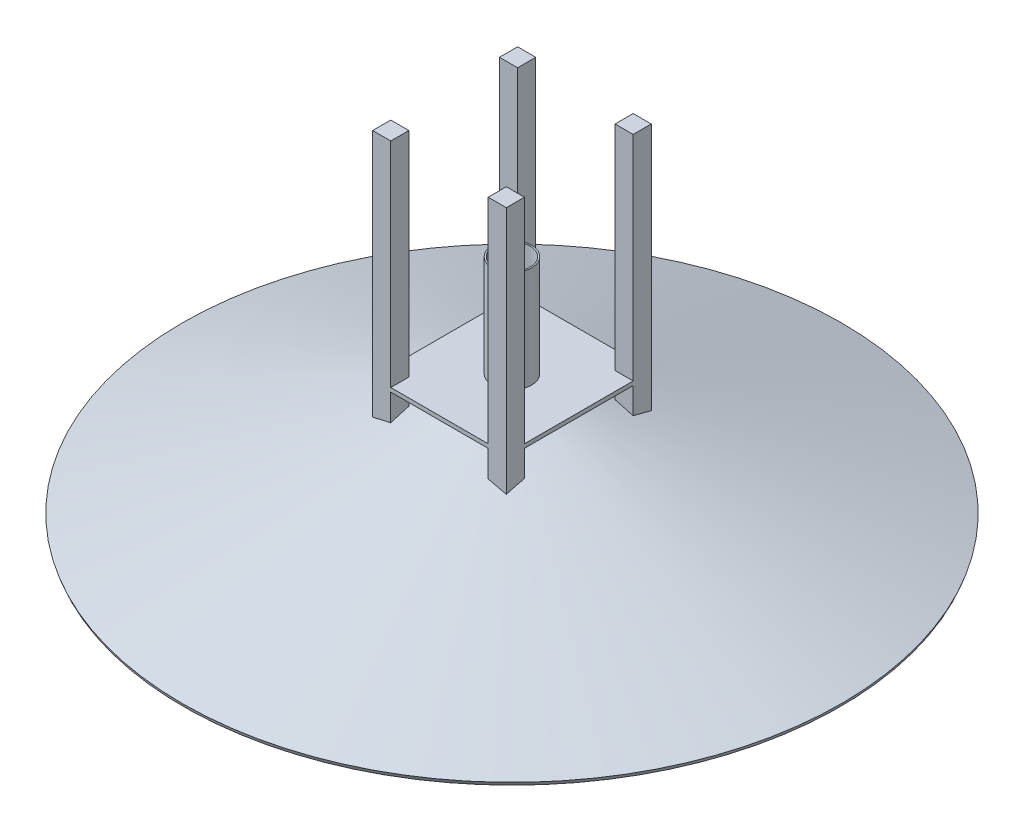
SolidWorks part; units mm, degrees
note: The reader was unsure of these and kept them because the rebuilt part matched: shared geometry of "Sketch1<11>", "Sketch1<12>", "Sketch1<13>", "Sketch1<14>".
material "Pine"
ref_plane "Front Plane" through (0, 0, 0) normal (0, 0, 1) x (1, 0, 0)
ref_plane "Top Plane" through (0, 0, 0) normal (0, 1, 0) x (1, 0, 0)
ref_plane "Right Plane" through (0, 0, 0) normal (1, 0, 0) x (0, 0, -1)
sketch "Sketch1" plane through (0, 0, 0) normal (0, 1, 0) x (1, 0, 0)
  line L0 (-187.325, 203.2) -> (-187.325, 152.4)
  line L1 (-187.325, -203.2) -> (187.325, -203.2)
  line L2 (-187.325, -203.2) -> (-187.325, 203.2)
  line L3 (-187.325, 203.2) -> (187.325, 203.2)
  line L4 (187.325, -203.2) -> (187.325, 203.2)
  line L5 (-187.325, -203.2) -> (187.325, 203.2) construction
  line L6 (-187.325, 203.2) -> (187.325, -203.2) construction
  line L7 (-187.325, 152.4) -> (-136.525, 152.4)
  line L8 (-136.525, 152.4) -> (-136.525, 203.2)
  line L9 (-136.525, 203.2) -> (-187.325, 203.2)
  line L10 (187.325, 203.2) -> (164.6437, 203.2)
  line L13 (187.325, 152.4) -> (187.325, 203.2)
  line L14 (136.525, 203.2) -> (136.525, 152.4)
  line L15 (136.525, 152.4) -> (187.325, 152.4)
  line L16 (187.325, 152.4) -> (187.325, 203.2)
  line L17 (187.325, 203.2) -> (136.525, 203.2)
  line L18 (136.525, -152.4) -> (136.525, -203.2)
  line L19 (136.525, -203.2) -> (187.325, -203.2)
  line L20 (187.325, -203.2) -> (187.325, -152.4)
  line L21 (187.325, -152.4) -> (136.525, -152.4)
  line L22 (-187.325, -152.4) -> (-187.325, -203.2)
  line L23 (-187.325, -203.2) -> (-136.525, -203.2)
  line L24 (-136.525, -203.2) -> (-136.525, -152.4)
  line L25 (-136.525, -152.4) -> (-187.325, -152.4)
  point P0 (0, 0)
  dimension "D1" = 374.65
  dimension "D2" = 406.4
  dimension "D3" = 50.8
  dimension "D4" = 50.8
  dimension "D5" = 50.8
  dimension "D6" = 50.8
  dimension "D7" = 50.8
  dimension "D8" = 50.8
  dimension "D9" = 50.8
  dimension "D10" = 50.8
extrude "Boss-Extrude2" add sketch "Sketch1" along normal blind 11.1125 contours L14 L15 L16 L17 | L2 L1 L4 L3 | L0 L7 L8 L9 | L24 L25 L22 L23 | L21 L18 L19 L20
extrude "Boss-Extrude3" add sketch "Sketch1<11>" along normal blind 609.6 contours L0 L7 L8 L9
sketch "Sketch1<11>" plane through (0, 0, 0) normal (0, 1, 0) x (1, 0, 0) same geometry as "Sketch1"
extrude "Boss-Extrude4" add sketch "Sketch1<12>" along normal blind 609.6 contours L25 L22 L23 L24
sketch "Sketch1<12>" plane through (0, 0, 0) normal (0, 1, 0) x (1, 0, 0) same geometry as "Sketch1"
extrude "Boss-Extrude5" add sketch "Sketch1<13>" along normal blind 609.6 contours L14 L15 L16 L17
sketch "Sketch1<13>" plane through (0, 0, 0) normal (0, 1, 0) x (1, 0, 0) same geometry as "Sketch1"
extrude "Boss-Extrude6" add sketch "Sketch1<14>" along normal blind 609.6 contours L21 L18 L19 L20
sketch "Sketch1<14>" plane through (0, 0, 0) normal (0, 1, 0) x (1, 0, 0) same geometry as "Sketch1"
sketch "Sketch4" plane through (0, 11.1125, 0) normal (0, 1, 0) x (1, 0, 0)
  circle A0 centre (0, 0) radius 50.8
  dimension "D1" = 101.6
extrude "Cut-Extrude2" cut sketch "Sketch4" against normal through all
sketch "Sketch5" plane through (0, 0, 0) normal (0, -1, 0) x (1, 0, 0)
  line L1 (-82.55, 76.2) -> (82.55, 76.2)
  line L2 (-82.55, 76.2) -> (-82.55, -76.2)
  line L3 (-82.55, -76.2) -> (82.55, -76.2)
  line L4 (82.55, 76.2) -> (82.55, -76.2)
  line L5 (-82.55, 76.2) -> (82.55, -76.2) construction
  line L6 (-82.55, -76.2) -> (82.55, 76.2) construction
  line L7 (-69.85, -63.5) -> (69.85, -63.5)
  line L8 (-69.85, -63.5) -> (-69.85, 63.5)
  line L9 (-69.85, 63.5) -> (69.85, 63.5)
  line L10 (69.85, -63.5) -> (69.85, 63.5)
  line L11 (-69.85, -63.5) -> (69.85, 63.5) construction
  line L12 (-69.85, 63.5) -> (69.85, -63.5) construction
  point P0 (0, 0)
  point P6 (0, 0)
  dimension "D1" = 152.4
  dimension "D2" = 165.1
  dimension "D3" = 139.7
  dimension "D4" = 127
extrude "Boss-Extrude8" add sketch "Sketch5" along normal blind 17.78 contours L8 L9 L10 L7 | L2 L3 L4 L1
sketch "Sketch11" plane through (0, -17.78, 0) normal (0, -1, 0) x (1, 0, 0)
  circle A0 centre (0, 0) radius 63.5 construction
sketch "Sketch12" plane through (0, 0, 0) normal (0, 0, 1) x (1, 0, 0)
  line L0 (0, -17.78) -> (0, -336.6621) construction
  line L1 (-63.5, -17.78) -> (63.5, -17.78) construction
  line L2 (-63.5, -17.78) -> (-920.4957, -336.6621)
  dimension "D1" = 914.4
revolve "Revolve-Thin1" add sketch "Sketch12" angle 360 about L0
sketch "Sketch13" plane through (0, 0, 0) normal (0, -1, 0) x (1, 0, 0)
  line L0 (-187.325, 203.2) -> (-187.325, 152.4)
  line L1 (-187.325, 152.4) -> (-136.525, 152.4)
  line L2 (-136.525, 152.4) -> (-136.525, 203.2)
  line L3 (-136.525, 203.2) -> (-187.325, 203.2)
  line L4 (136.525, 203.2) -> (187.325, 203.2)
  line L5 (187.325, 203.2) -> (187.325, 152.4)
  line L6 (187.325, 152.4) -> (136.525, 152.4)
  line L7 (136.525, 152.4) -> (136.525, 203.2)
  line L8 (187.325, -152.4) -> (136.525, -152.4)
  line L9 (136.525, -152.4) -> (136.525, -203.2)
  line L10 (136.525, -203.2) -> (187.325, -203.2)
  line L11 (187.325, -203.2) -> (187.325, -152.4)
  line L12 (-136.525, -152.4) -> (-187.325, -152.4)
  line L13 (-187.325, -152.4) -> (-187.325, -203.2)
  line L14 (-187.325, -203.2) -> (-136.525, -203.2)
  line L15 (-136.525, -203.2) -> (-136.525, -152.4)
extrude "Boss-Extrude9" add sketch "Sketch13" along normal blind 381
sketch "Sketch14" plane through (0, 11.1125, 0) normal (0, 1, 0) x (1, 0, 0)
  circle A0 centre (0, 0) radius 55
  circle A1 centre (0, 0) radius 50.9026
  dimension "D1" = 110
extrude "Boss-Extrude10" add sketch "Sketch14" along normal blind 284.5
